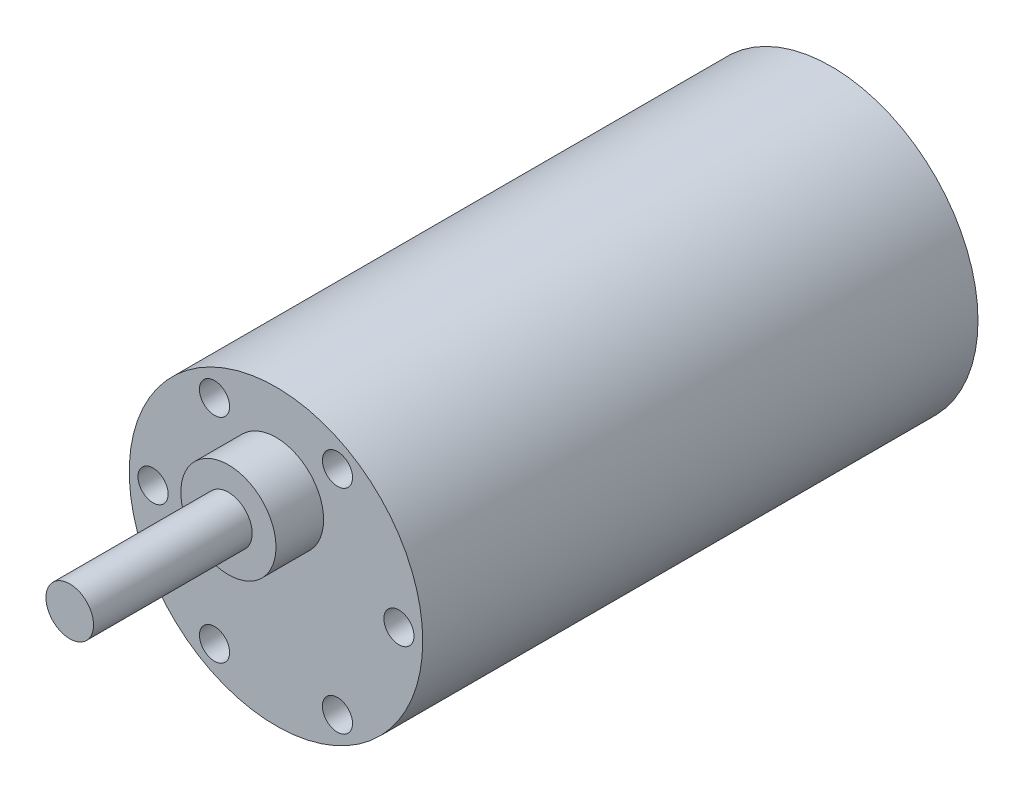
SolidWorks part; units mm, degrees
ref_plane "Front Plane" through (0, 0, 0) normal (1, 0, 0) x (0, 1, 0)
ref_plane "Top Plane" through (0, 0, 0) normal (0, 0, 1) x (0, 1, 0)
ref_plane "Right Plane" through (0, 0, 0) normal (0, 1, 0) x (-1, 0, 0)
sketch "Sketch1" plane through (0, 0, 0) normal (0, 0, 1) x (0, 1, 0)
  circle A0 centre (0, 0) radius 18.5
  dimension "D1" = 37
extrude "Boss-Extrude1" add sketch "Sketch1" along normal blind 70
sketch "Sketch2" plane through (0, 0, 70) normal (0, 0, 1) x (-1, 0, 0)
  circle A7 centre (0, -7) radius 6
  circle A9 centre (0, 0) radius 18.5 construction
  circle A21 centre (0, 0) radius 15.5 construction
  circle A22 centre (-15.5, 0) radius 1.9
  circle A23 centre (-7.75, 13.4234) radius 1.9
  circle A24 centre (7.75, 13.4234) radius 1.9
  circle A25 centre (15.5, 0) radius 1.9
  circle A26 centre (7.75, -13.4234) radius 1.9
  circle A27 centre (-7.75, -13.4234) radius 1.9
  dimension "D2" = 37
  dimension "D14" = 31
  dimension "D15" = 3.8
  dimension "D6" = 12
  dimension "D13" = 7
  dimension "D16" = 6
extrude "Cut-Extrude1" cut sketch "Sketch2" against normal blind 3 contours A22 | A23 | A24 | A25 | A26 | A27 region at (15.5, 0, 70) region at (7.75, -13.4234, 70) region at (-7.75, -13.4234, 70) region at (-15.5, 0, 70) region at (-7.75, 13.4234, 70) region at (7.75, 13.4234, 70)
extrude "Boss-Extrude2" add sketch "Sketch2<3>" along normal blind 6 contours A7 region at (0, 7, 70)
sketch "Sketch2<3>" plane through (0, 0, 70) normal (0, 0, 1) x (-1, 0, 0) same geometry as "Sketch2"
sketch "Sketch3" plane through (0, 0, 76) normal (0, 0, 1) x (1, 0, 0)
  circle A0 centre (0, 7) radius 3
  dimension "D1" = 6
extrude "Boss-Extrude3" add sketch "Sketch3" along normal blind 20
